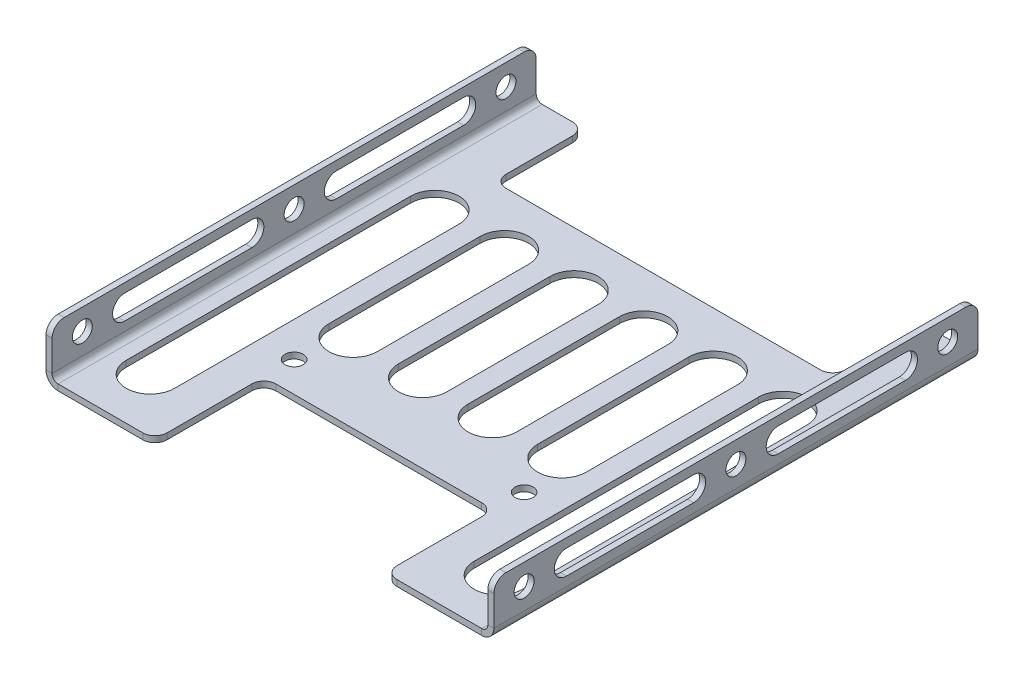
SolidWorks part; units mm, degrees
note: The reader was unsure of these and kept them because the rebuilt part matched: bend radius of "基体折弯1", "基体折弯2".
material "6061 合金"
ref_plane "前视基准面" through (0, 0, 0) normal (0, 0, 1) x (1, 0, 0)
ref_plane "上视基准面" through (0, 0, 0) normal (0, 1, 0) x (1, 0, 0)
ref_plane "右视基准面" through (0, 0, 0) normal (1, 0, 0) x (0, 0, -1)
sketch "草图1" plane through (0, 0, 0) normal (0, 0, 1) x (1, 0, 0)
  line L0 (-36, 8) -> (-36, 0)
  line L1 (-36, 0) -> (36, 0)
  line L2 (36, 0) -> (36, 8)
  dimension "D1" = 8
  dimension "D2" = 72
base flange "基体-法兰1" sketch "草图1" end condition mid plane depth 80 reverse direction no thickness 1 reverse thickness direction no bend radius 1
bend "基体折弯1" bend radius 1 bend angle 90 parameters "D5"=1
bend "基体折弯2" bend radius 1 bend angle 90 parameters "D5"=2
sketch "草图6" plane through (0, 0, 0) normal (1, 0, 0) x (0, 0, -1)
  line L0 (-35, 4.5) -> (35, 4.5) construction
  line L1 (0, 4.5) -> (0, 0) construction
  line L4 (-40, 8) -> (40, 8) construction
  circle A0 centre (-35, 4.5) radius 1.65
  circle A1 centre (35, 4.5) radius 1.65
  circle A4 centre (0, 4.5) radius 1.65
  dimension "D3" = 3.3
  dimension "D2" = 3.5
  dimension "D1" = 70
extrude "切除-拉伸1" cut sketch "草图6" against normal through all both and the other way through all
sketch "草图8" plane through (0, 0, 0) normal (1, 0, 0) x (0, 0, -1)
  line L0 (-28, 4.5) -> (-7, 4.5) construction
  line L1 (-28, 6.5) -> (-7, 6.5)
  line L2 (-28, 2.5) -> (-7, 2.5)
  line L3 (-28, 4.5) -> (-35, 4.5) construction
  line L4 (-7, 4.5) -> (0, 4.5) construction
  line L5 (0, 4.95) -> (0, -4.95) construction
  line L6 (28, 4.5) -> (7, 4.5) construction
  line L7 (28, 6.5) -> (7, 6.5)
  line L8 (28, 2.5) -> (7, 2.5)
  arc A0 (-28, 6.5) -> (-28, 2.5) centre (-28, 4.5) ccw
  arc A1 (-7, 2.5) -> (-7, 6.5) centre (-7, 4.5) ccw
  arc A2 (28, 6.5) -> (28, 2.5) centre (28, 4.5) cw
  arc A3 (7, 2.5) -> (7, 6.5) centre (7, 4.5) cw
  point P2 (-17.5, 4.5)
  point P13 (-30, 4.5)
  point P14 (-5, 4.5)
  point P19 (17.5, 4.5)
  dimension "D1" = 25
  dimension "D2" = 4
extrude "切除-拉伸3" cut sketch "草图8" against normal through all both and the other way through all normal cut yes
sketch "草图7" plane through (0, -1, 0) normal (0, -1, 0) x (1, 0, 0)
  line L0 (-28.75, 31) -> (-28.75, -16) construction
  line L1 (-24.75, 31) -> (-24.75, -16)
  line L2 (-32.75, 31) -> (-32.75, -16)
  line L3 (-35, 40) -> (35, 40) construction
  line L4 (-35, -40) -> (35, -40) construction
  line L5 (-17.25, 9) -> (-17.25, -16) construction
  line L6 (-13.25, 9) -> (-13.25, -16)
  line L7 (-21.25, 9) -> (-21.25, -16)
  line L8 (-5.75, 9) -> (-5.75, -16) construction
  line L9 (-1.75, 9) -> (-1.75, -16)
  line L10 (-9.75, 9) -> (-9.75, -16)
  line L11 (17.25, 9) -> (17.25, -16) construction
  line L12 (21.25, 9) -> (21.25, -16)
  line L13 (13.25, 9) -> (13.25, -16)
  line L14 (28.75, 31) -> (28.75, -16) construction
  line L15 (32.75, 31) -> (32.75, -16)
  line L16 (24.75, 31) -> (24.75, -16)
  line L17 (-28, -40) -> (28, -40)
  line L18 (-28, -40) -> (-28, -25)
  line L19 (-28, -25) -> (28, -25)
  line L20 (28, -40) -> (28, -25)
  line L21 (-28.75, -20) -> (28.75, -20) construction
  line L22 (5.75, 9) -> (5.75, -16) construction
  line L23 (9.75, 9) -> (9.75, -16)
  line L24 (1.75, 9) -> (1.75, -16)
  line L25 (0, 0) -> (0, -25) construction
  line L28 (-19, 17) -> (19, 17) construction
  line L30 (-19, 40) -> (19, 40)
  line L31 (-19, 40) -> (-19, 22)
  line L32 (-19, 22) -> (19, 22)
  line L33 (19, 40) -> (19, 22)
  arc A0 (-24.75, 31) -> (-32.75, 31) centre (-28.75, 31) ccw
  arc A1 (-32.75, -16) -> (-24.75, -16) centre (-28.75, -16) ccw
  arc A2 (-13.25, 9) -> (-21.25, 9) centre (-17.25, 9) ccw
  arc A3 (-21.25, -16) -> (-13.25, -16) centre (-17.25, -16) ccw
  arc A4 (-1.75, 9) -> (-9.75, 9) centre (-5.75, 9) ccw
  arc A5 (-9.75, -16) -> (-1.75, -16) centre (-5.75, -16) ccw
  arc A6 (21.25, 9) -> (13.25, 9) centre (17.25, 9) ccw
  arc A7 (13.25, -16) -> (21.25, -16) centre (17.25, -16) ccw
  arc A8 (32.75, 31) -> (24.75, 31) centre (28.75, 31) ccw
  arc A9 (24.75, -16) -> (32.75, -16) centre (28.75, -16) ccw
  arc A10 (9.75, 9) -> (1.75, 9) centre (5.75, 9) ccw
  arc A11 (1.75, -16) -> (9.75, -16) centre (5.75, -16) ccw
  circle A16 centre (19, 17) radius 1.5
  circle A17 centre (-19, 17) radius 1.5
  point P2 (-28.75, 7.5)
  point P7 (-28.75, 35)
  point P16 (-17.25, -3.5)
  point P22 (-5.75, -3.5)
  point P29 (17.25, -3.5)
  point P36 (28.75, 7.5)
  point P43 (-17.25, 13)
  point P47 (-17.25, -20)
  point P48 (0, 22)
  point P50 (0, -20)
  point P52 (0, 17)
  point P55 (5.75, -3.5)
  dimension "D12" = 23
  dimension "D14" = 3
  dimension "D1" = 8
  dimension "D2" = 5
  dimension "D3" = 3.5
  dimension "D5" = 56
  dimension "D4" = 5
  dimension "D6" = 15
  dimension "D7" = 3.5
  dimension "D8" = 3.5
  dimension "D9" = 3.5
  dimension "D10" = 3.5
  dimension "D11" = 38
  dimension "D13" = 33
  dimension "D15" = 38
  dimension "D16" = 5
extrude "切除-拉伸2" cut sketch "草图7" against normal blind 10
fillet "圆角1" radius 2 12 edges at (36.5, 8, 40) (36.5, 8, -40) (-36.5, 8, -40) (-36.5, 8, 40) (-28, -0.5, -25) (28, -0.5, -25) (-28, -0.5, -40) (28, -0.5, -40) (19, -0.5, 40) (19, -0.5, 22) (-19, -0.5, 22) (-19, -0.5, 40)
sketch "折弯-线1" [suppressed] plane through (0, 0, 0) normal (0, 1, 0) x (1, 0, 0)
sketch "边界框1" [suppressed] plane through (0, 0, 0) normal (0, 1, 0) x (1, 0, 0)
sheet metal parameters "钣金6" thickness 1 parameters "D1"=1
flat pattern "平板型式6" [suppressed]
sketch "折弯-线2" plane through (0, 0, 0) normal (0, 1, 0) x (1, 0, 0)
sketch "边界框2" [suppressed] plane through (0, 0, 0) normal (0, 1, 0) x (1, 0, 0)
bend of the flat pattern "展平-<基体折弯1>1"
bend of the flat pattern "展平-<基体折弯2>1"
sheet metal parameters "钣金7" thickness 1 parameters "D1"=1
flat pattern "平板型式6" [suppressed]
sketch "折弯-线2" plane through (0, 0, 0) normal (0, 1, 0) x (1, 0, 0)
sketch "边界框2" [suppressed] plane through (0, 0, 0) normal (0, 1, 0) x (1, 0, 0)
bend of the flat pattern "展平-<基体折弯1>1"
bend of the flat pattern "展平-<基体折弯2>1"
sheet metal parameters "钣金8" thickness 1 parameters "D1"=1
flat pattern "平板型式6"
sketch "折弯-线2" plane through (0, 0, 0) normal (0, 1, 0) x (1, 0, 0)
  line L0 (-36.1781, -40) -> (-36.1781, 40) construction
  line L1 (36.1781, 40) -> (36.1781, -40) construction
  line L2 (-36.1781, -40) -> (-36.1781, 40) construction
  line L3 (36.1781, 40) -> (36.1781, -40) construction
sketch3d "边界框2" [suppressed]
  line L0 (-8.3562, 0, 0) -> (80.3562, 0, 0) construction
  line L1 (-8.3562, 80, 0) -> (80.3562, 80, 0) construction
  line L2 (-8.3562, 0, 0) -> (-8.3562, 80, 0) construction
  line L3 (80.3562, 0, 0) -> (80.3562, 80, 0) construction
bend of the flat pattern "展平-<基体折弯1>1"
bend of the flat pattern "展平-<基体折弯2>1"
sheet metal parameters "钣金9" thickness 1 parameters "D1"=1
flat pattern "平板型式6"
sketch "折弯-线2" plane through (0, 0, 0) normal (0, 1, 0) x (1, 0, 0)
  line L0 (-31.1781, -17.5) -> (-31.1781, 17.5) construction
  line L1 (31.1781, 17.5) -> (31.1781, -17.5) construction
  line L2 (-31.1781, -17.5) -> (-31.1781, 17.5) construction
  line L3 (31.1781, 17.5) -> (31.1781, -17.5) construction
sketch3d "边界框2" [suppressed]
  line L0 (-9.3562, 0, 0) -> (71.3562, 0, 0) construction
  line L1 (-9.3562, 35, 0) -> (71.3562, 35, 0) construction
  line L2 (-9.3562, 0, 0) -> (-9.3562, 35, 0) construction
  line L3 (71.3562, 0, 0) -> (71.3562, 35, 0) construction
bend of the flat pattern "展平-<基体折弯1>1"
bend of the flat pattern "展平-<基体折弯2>1"
